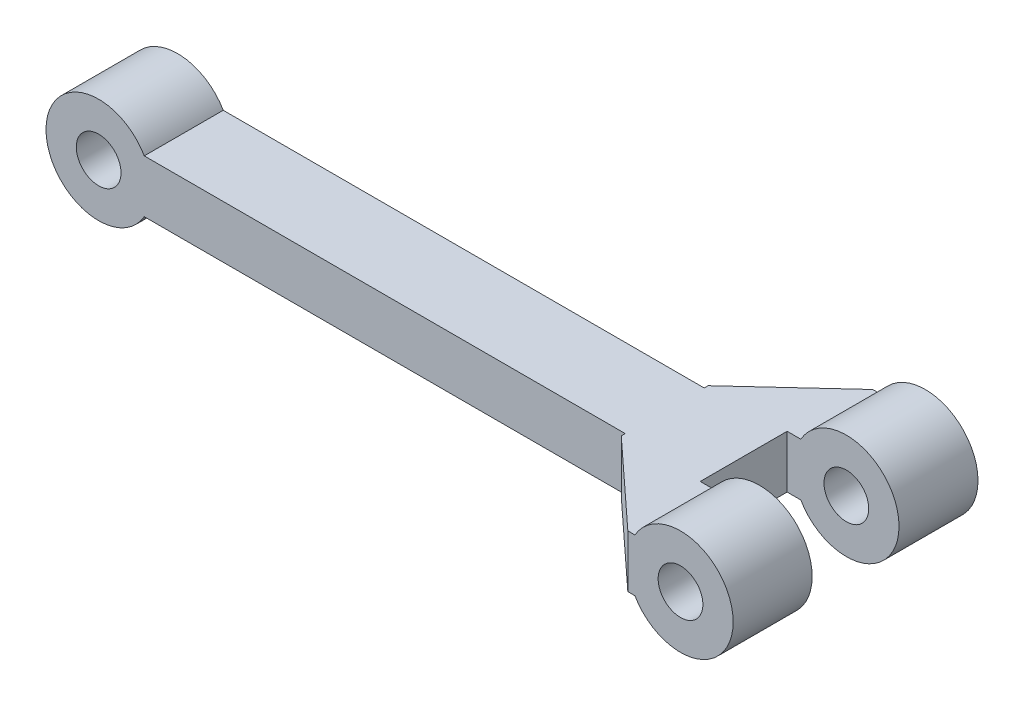
SolidWorks part; units mm, degrees
ref_plane "Спереди" through (0, 0, 0) normal (0, 0, 1) x (1, 0, 0)
ref_plane "Сверху" through (0, 0, 0) normal (0, 1, 0) x (1, 0, 0)
ref_plane "Справа" through (0, 0, 0) normal (1, 0, 0) x (0, 0, -1)
other "Configuration Table"
sketch "Эскиз1" plane through (0, 0, 0) normal (0, 0, 1) x (1, 0, 0)
  circle A0 centre (0, 0) radius 1.7
  circle A1 centre (0, 0) radius 4
  dimension "D1" = 3.4
  dimension "D2" = 8
extrude "Бобышка-Вытянуть1" add sketch "Эскиз1" along normal blind 6
sketch "Эскиз2" plane through (0, 0, 0) normal (0, 1, 0) x (1, 0, 0)
  line L0 (-4, 0) -> (-10.5, -6)
  line L1 (-10.5, -6) -> (-10.5, -12.6)
  line L2 (-10.5, -12.6) -> (-4, -18.6)
  line L4 (-4, -12.6) -> (-4.5, -12.6)
  line L5 (-4.5, -12.6) -> (-4.5, -6)
  line L6 (-4.5, -6) -> (-4, -6)
  line L7 (-4, 0) -> (-4, -6) construction
  line L9 (2.5677, -9.3) -> (-17.3387, -9.3) construction
  line L10 (-4, -6) -> (4, -6) construction
  line L11 (-4, 0) -> (-3, 0)
  line L12 (-3, 0) -> (-3, -6)
  line L13 (-3, -6) -> (-4, -6)
  line L14 (-4, -12.6) -> (-3, -12.6)
  line L15 (-3, -12.6) -> (-3, -18.6)
  line L16 (-3, -18.6) -> (-4, -18.6)
  dimension "D1" = 3.3
  dimension "D2" = 6
  dimension "D3" = 0.5
  dimension "D4" = 6
  dimension "D5" = 1
  dimension "D6" = 1
extrude "Бобышка-Вытянуть2" add sketch "Эскиз2" along normal blind 2 and the other way blind 2
ref_plane "Плоскость1" through (0, 0, 9.3) normal (0, 0, -1) x (-1, 0, 0)
mirror "Зеркальное отражение1" about plane through (0, 0, 9.3) normal (0, 0, -1) of "Бобышка-Вытянуть1"
sketch "Эскиз3" plane through (0, 0, 9.3) normal (0, 0, -1) x (-1, 0, 0)
  line L10 (1.741, 0) -> (46.1169, 0) construction
  line L12 (10.5, 2) -> (47.0359, 2)
  line L14 (10.5, -2) -> (47.0359, -2)
  line L15 (10.5, 2) -> (10.5, -2)
  circle A9 centre (50.5, 0) radius 1.7
  arc A10 (47.0359, -2) -> (47.0359, 2) centre (50.5, 0) ccw
  dimension "D2" = 8
  dimension "D3" = 40
  dimension "D1" = 3.4
extrude "Бобышка-Вытянуть3" add sketch "Эскиз3" along normal blind 3 and the other way blind 3
